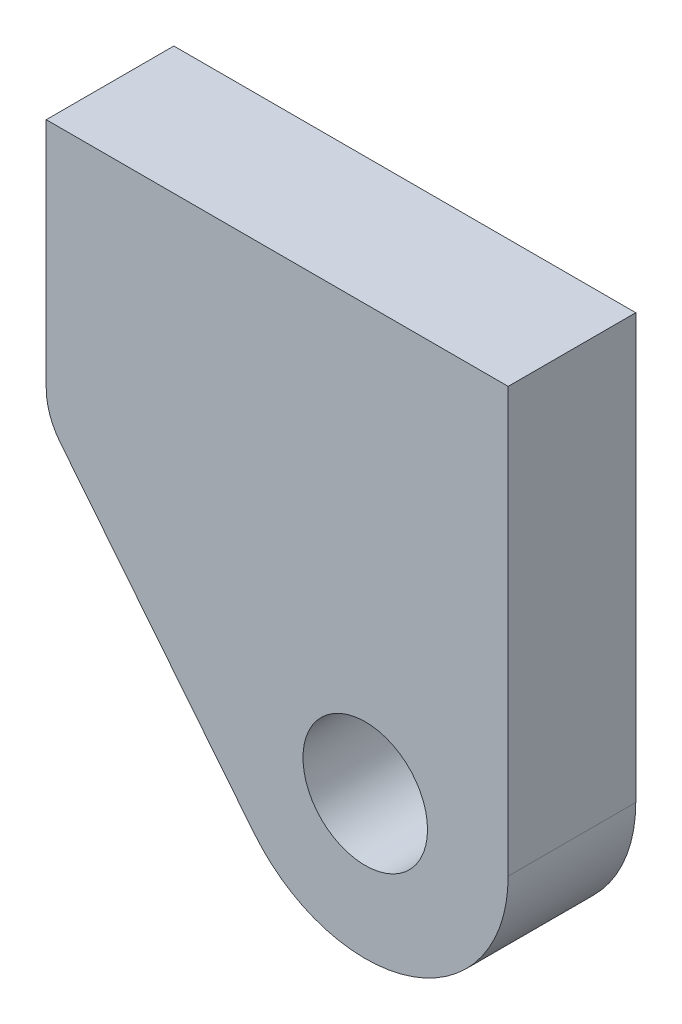
SolidWorks part; units mm, degrees
ref_plane "Front Plane" through (0, 0, 0) normal (0, 0, 1) x (1, 0, 0)
ref_plane "Top Plane" through (0, 0, 0) normal (0, 1, 0) x (1, 0, 0)
ref_plane "Right Plane" through (0, 0, 0) normal (1, 0, 0) x (0, 0, -1)
sketch "Sketch1" plane through (0, 0, 0) normal (0, 0, 1) x (1, 0, 0)
  line L0 (-5.7468, 0) -> (5.7468, 0)
  line L1 (-5.7468, 0) -> (-5.7467, -5.7914)
  line L2 (5.7468, 0) -> (5.7468, -10.5537)
  line L3 (-5.3969, -6.7855) -> (-0.5817, -12.7805)
  arc A0 (5.7468, -10.5537) -> (-0.5817, -12.7805) centre (2.1908, -10.5537) cw
  circle A1 centre (2.1908, -10.5537) radius 1.5494
  arc A2 (-5.3969, -6.7855) -> (-5.7467, -5.7914) centre (-4.1592, -5.7914) cw
  point P4 (0, 0)
  point P12 (-5.7467, -6.35)
  dimension "D4" = 3.556
  dimension "D5" = 3.0988
  dimension "D6" = 1.5875
  dimension "D1" = 11.4935
  dimension "D2" = 6.35
  dimension "D3" = 10.5537
extrude "Boss-Extrude1" add sketch "Sketch1" along normal mid plane 3.175 contours A0 L2 L0 L1 L3 A1 region at (0.4612, -5.8436, 0)
